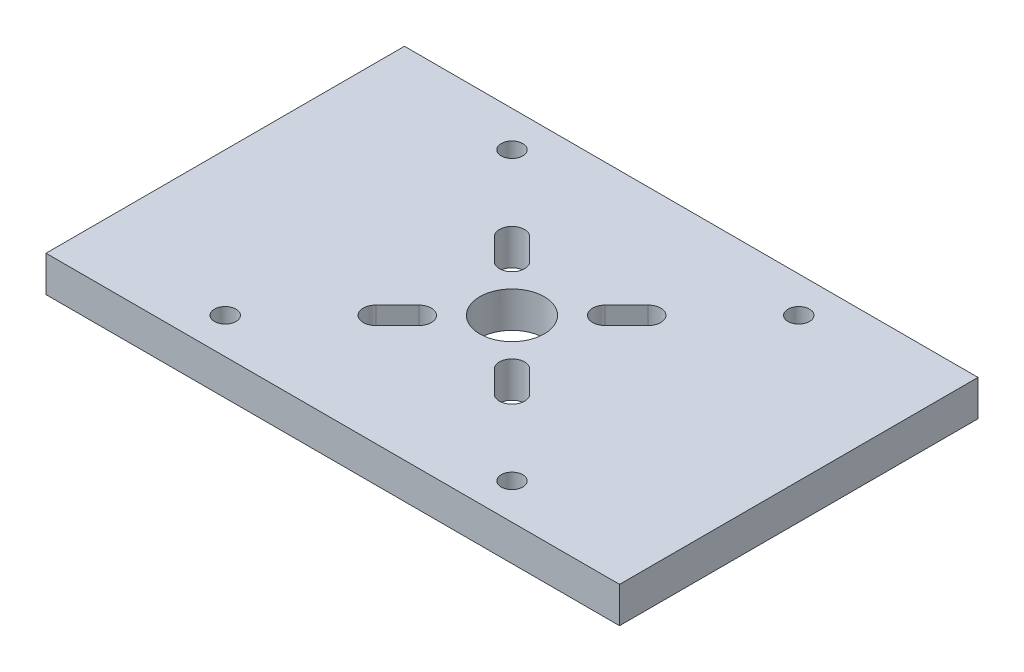
SolidWorks part; units mm, degrees
ref_plane "Front Plane" through (0, 0, 0) normal (0, 0, 1) x (1, 0, 0)
ref_plane "Top Plane" through (0, 0, 0) normal (0, 1, 0) x (1, 0, 0)
ref_plane "Right Plane" through (0, 0, 0) normal (1, 0, 0) x (0, 0, -1)
sketch "Sketch1" plane through (0, 0, 0) normal (0, 1, 0) x (1, 0, 0)
  line L1 (80, 50) -> (-80, 50)
  line L2 (80, 50) -> (80, -50)
  line L3 (80, -50) -> (-80, -50)
  line L4 (-80, 50) -> (-80, -50)
  line L5 (80, 50) -> (-80, -50) construction
  line L6 (80, -50) -> (-80, 50) construction
  point P0 (0, 0)
  dimension "D1" = 160
  dimension "D2" = 100
extrude "base" add sketch "Sketch1" along normal blind 10 contours L1 L4 L3 L2
sketch "Sketch2" plane through (0, 10, 0) normal (0, 1, 0) x (1, 0, 0)
  circle A0 centre (0, 0) radius 9
  dimension "D1" = 18
extrude "actuator cut" cut sketch "Sketch2" against normal blind 40
sketch "Sketch3" plane through (0, 10, 0) normal (0, 1, 0) x (1, 0, 0)
  line L0 (19, -19) -> (13, -13) construction
  line L1 (0, 0) -> (0, 19) construction
  line L2 (-19, -19) -> (19, 19) construction
  line L3 (-19, -19) -> (-13, -13) construction
  line L4 (-21.4749, -16.5251) -> (-15.4749, -10.5251)
  line L5 (-16.5251, -21.4749) -> (-10.5251, -15.4749)
  line L6 (21.4749, -16.5251) -> (15.4749, -10.5251)
  line L7 (16.5251, -21.4749) -> (10.5251, -15.4749)
  line L8 (0, 0) -> (19, 0) construction
  line L9 (19, 19) -> (13, 13) construction
  line L10 (21.4749, 16.5251) -> (15.4749, 10.5251)
  line L11 (16.5251, 21.4749) -> (10.5251, 15.4749)
  line L12 (-19, 19) -> (-13, 13) construction
  line L13 (-21.4749, 16.5251) -> (-15.4749, 10.5251)
  line L14 (-16.5251, 21.4749) -> (-10.5251, 15.4749)
  arc A4 (-21.4749, -16.5251) -> (-16.5251, -21.4749) centre (-19, -19) ccw
  arc A5 (-10.5251, -15.4749) -> (-15.4749, -10.5251) centre (-13, -13) ccw
  arc A6 (21.4749, -16.5251) -> (16.5251, -21.4749) centre (19, -19) cw
  arc A7 (10.5251, -15.4749) -> (15.4749, -10.5251) centre (13, -13) cw
  arc A8 (21.4749, 16.5251) -> (16.5251, 21.4749) centre (19, 19) ccw
  arc A9 (10.5251, 15.4749) -> (15.4749, 10.5251) centre (13, 13) ccw
  arc A10 (-21.4749, 16.5251) -> (-16.5251, 21.4749) centre (-19, 19) cw
  arc A11 (-10.5251, 15.4749) -> (-15.4749, 10.5251) centre (-13, 13) cw
  point P1 (-16, -16)
  point P10 (16, -16)
  point P20 (16, 16)
  point P27 (-16, 16)
  dimension "D5" = 3.5
  dimension "D4" = 19
  dimension "D1" = 13
  dimension "D2" = 19
  dimension "D3" = 45
  dimension "D6" = 19
extrude "Cut-Extrude1" cut sketch "Sketch3" against normal up to next
sketch "Sketch4" plane through (0, 0, 0) normal (0, -1, 0) x (1, 0, 0)
  line L0 (21.4749, 16.5251) -> (15.4749, 10.5251) construction
  line L1 (10.5251, 15.4749) -> (16.5251, 21.4749) construction
  line L2 (-15.4749, 10.5251) -> (-21.4749, 16.5251) construction
  line L3 (-16.5251, 21.4749) -> (-10.5251, 15.4749) construction
  line L4 (-10.5251, -15.4749) -> (-16.5251, -21.4749) construction
  line L5 (-21.4749, -16.5251) -> (-15.4749, -10.5251) construction
  line L6 (16.5251, -21.4749) -> (10.5251, -15.4749) construction
  line L7 (15.4749, -10.5251) -> (21.4749, -16.5251) construction
  line L8 (21.4749, 16.5251) -> (15.4749, 10.5251) construction
  line L9 (10.5251, 15.4749) -> (16.5251, 21.4749) construction
  line L10 (-15.4749, 10.5251) -> (-21.4749, 16.5251) construction
  line L11 (-16.5251, 21.4749) -> (-10.5251, 15.4749) construction
  line L12 (-10.5251, -15.4749) -> (-16.5251, -21.4749) construction
  line L13 (-21.4749, -16.5251) -> (-15.4749, -10.5251) construction
  line L14 (16.5251, -21.4749) -> (10.5251, -15.4749) construction
  line L15 (15.4749, -10.5251) -> (21.4749, -16.5251) construction
  line L16 (23.2426, 14.7574) -> (17.2426, 8.7574)
  line L17 (8.7574, 17.2426) -> (14.7574, 23.2426)
  line L18 (-17.2426, 8.7574) -> (-23.2426, 14.7574)
  line L19 (-14.7574, 23.2426) -> (-8.7574, 17.2426)
  line L20 (-8.7574, -17.2426) -> (-14.7574, -23.2426)
  line L21 (-23.2426, -14.7574) -> (-17.2426, -8.7574)
  line L22 (14.7574, -23.2426) -> (8.7574, -17.2426)
  line L23 (17.2426, -8.7574) -> (23.2426, -14.7574)
  arc A0 (10.5251, 15.4749) -> (15.4749, 10.5251) centre (13, 13) ccw construction
  arc A1 (21.4749, 16.5251) -> (16.5251, 21.4749) centre (19, 19) ccw construction
  arc A2 (-16.5251, 21.4749) -> (-21.4749, 16.5251) centre (-19, 19) ccw construction
  arc A3 (-15.4749, 10.5251) -> (-10.5251, 15.4749) centre (-13, 13) ccw construction
  arc A4 (-21.4749, -16.5251) -> (-16.5251, -21.4749) centre (-19, -19) ccw construction
  arc A5 (-10.5251, -15.4749) -> (-15.4749, -10.5251) centre (-13, -13) ccw construction
  arc A6 (15.4749, -10.5251) -> (10.5251, -15.4749) centre (13, -13) ccw construction
  arc A7 (16.5251, -21.4749) -> (21.4749, -16.5251) centre (19, -19) ccw construction
  arc A8 (10.5251, 15.4749) -> (15.4749, 10.5251) centre (13, 13) ccw construction
  arc A9 (21.4749, 16.5251) -> (16.5251, 21.4749) centre (19, 19) ccw construction
  arc A10 (-16.5251, 21.4749) -> (-21.4749, 16.5251) centre (-19, 19) ccw construction
  arc A11 (-15.4749, 10.5251) -> (-10.5251, 15.4749) centre (-13, 13) ccw construction
  arc A12 (-21.4749, -16.5251) -> (-16.5251, -21.4749) centre (-19, -19) ccw construction
  arc A13 (-10.5251, -15.4749) -> (-15.4749, -10.5251) centre (-13, -13) ccw construction
  arc A14 (15.4749, -10.5251) -> (10.5251, -15.4749) centre (13, -13) ccw construction
  arc A15 (16.5251, -21.4749) -> (21.4749, -16.5251) centre (19, -19) ccw construction
  arc A16 (8.7574, 17.2426) -> (17.2426, 8.7574) centre (13, 13) ccw
  arc A17 (23.2426, 14.7574) -> (14.7574, 23.2426) centre (19, 19) ccw
  arc A18 (-14.7574, 23.2426) -> (-23.2426, 14.7574) centre (-19, 19) ccw
  arc A19 (-17.2426, 8.7574) -> (-8.7574, 17.2426) centre (-13, 13) ccw
  arc A20 (-23.2426, -14.7574) -> (-14.7574, -23.2426) centre (-19, -19) ccw
  arc A21 (-8.7574, -17.2426) -> (-17.2426, -8.7574) centre (-13, -13) ccw
  arc A22 (17.2426, -8.7574) -> (8.7574, -17.2426) centre (13, -13) ccw
  arc A23 (14.7574, -23.2426) -> (23.2426, -14.7574) centre (19, -19) ccw
  dimension "D1" = 2.5
split line "Split Line1"
sketch "Sketch5" plane through (0, 10, 0) normal (0, 1, 0) x (1, 0, 0)
  line L0 (-40, 40) -> (-40, -40) construction
  line L1 (-40, -40) -> (40, -40) construction
  circle A0 centre (-40, -40) radius 3
  circle A1 centre (-40, 40) radius 3
  circle A2 centre (40, -40) radius 3
  circle A3 centre (40, 40) radius 3
  point P8 (-40, 0)
  point P9 (0, -40)
  dimension "D3" = 6
  dimension "D1" = 80
  dimension "D2" = 80
extrude "Cut-Extrude2" cut sketch "Sketch5" against normal up to next
equation "\"D4@Sketch3\"=\"D2@Sketch3\""
equation "\"D6@Sketch3\"=\"D2@Sketch3\""
